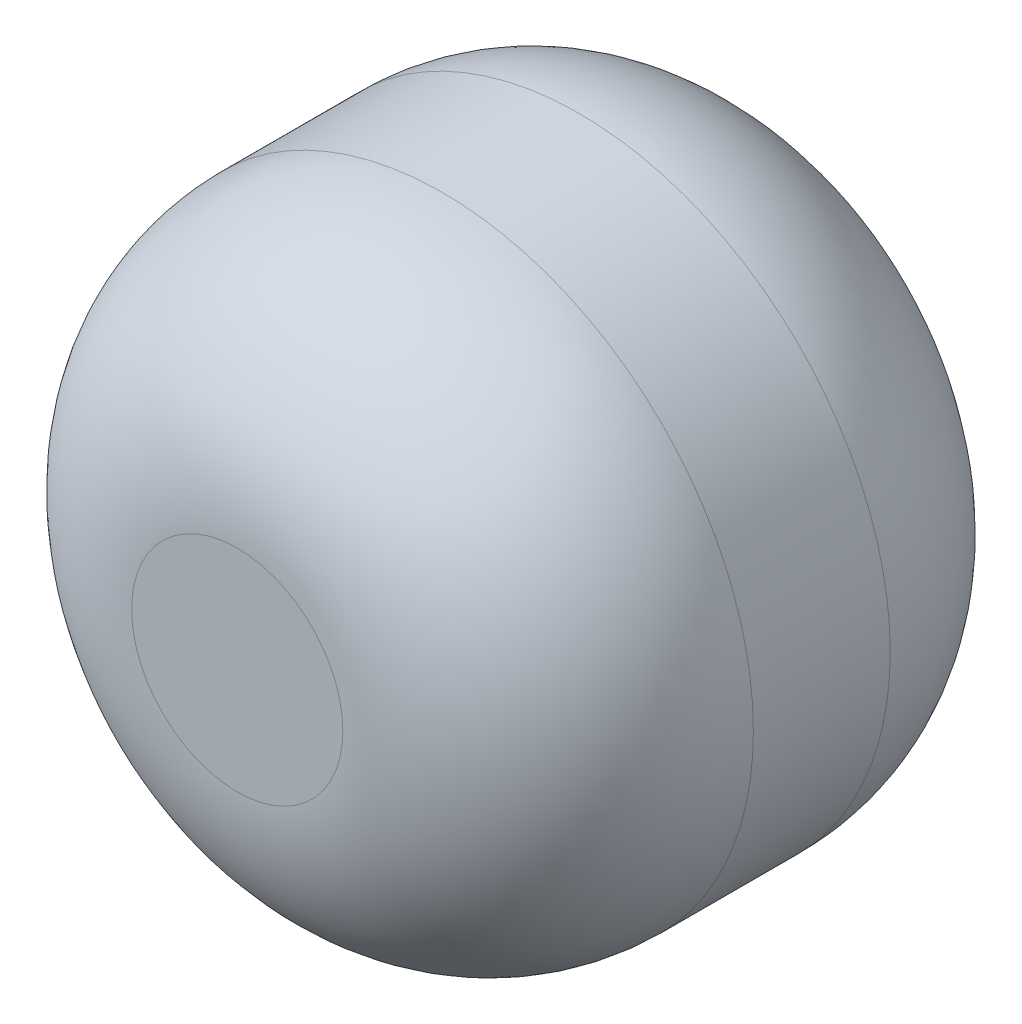
SolidWorks part; units mm, degrees
ref_plane "Ebene vorne" through (0, 0, 0) normal (0, 0, 1) x (1, 0, 0)
ref_plane "Ebene oben" through (0, 0, 0) normal (0, 1, 0) x (1, 0, 0)
ref_plane "Ebene rechts" through (0, 0, 0) normal (1, 0, 0) x (0, 0, -1)
sketch "Skizze1" plane through (0, 0, 0) normal (0, 0, 1) x (1, 0, 0)
  circle A0 centre (17.0042, 109.6946) radius 45.4385 construction
  circle A1 centre (17.0042, 109.6946) radius 45.4385
extrude "Aufsatz-Linear austragen1" add sketch "Skizze1" along normal blind 80
fillet "Verrundung1" radius 30 2 edges at (62.4426, 109.6946, 0) (62.4426, 109.6946, 80)
